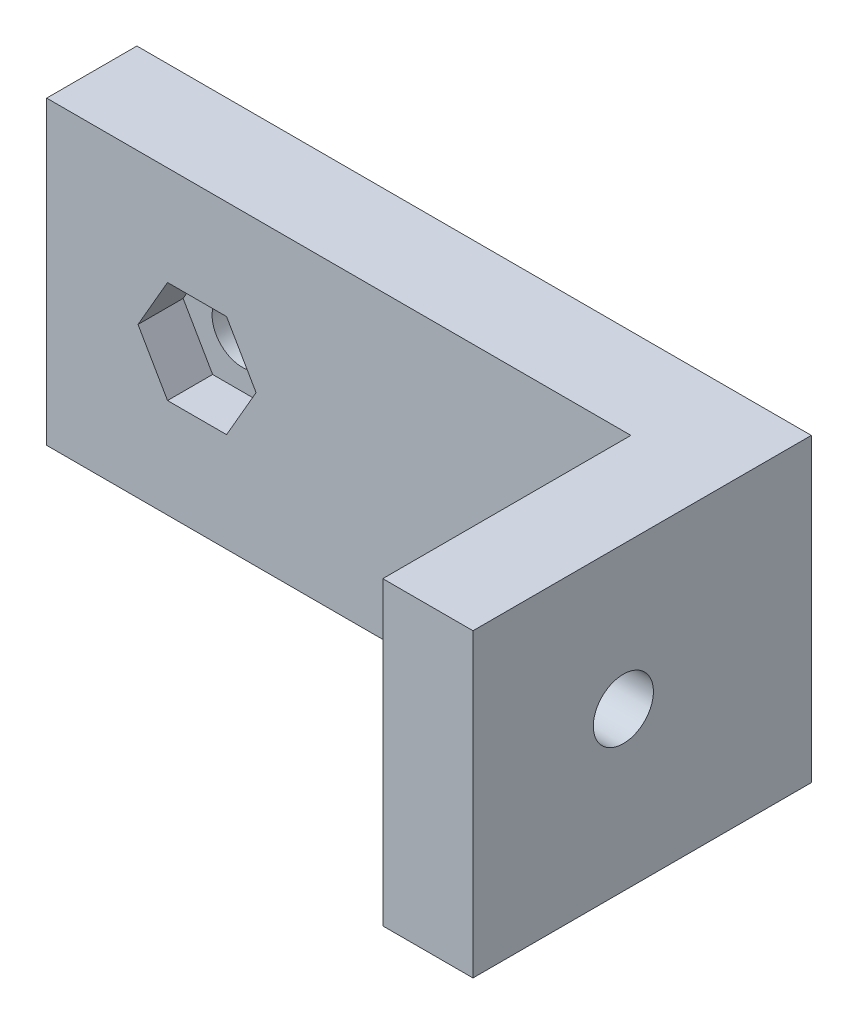
SolidWorks part; units mm, degrees
material "ABS"
ref_plane "Front Plane" through (0, 0, 0) normal (0, 0, 1) x (1, 0, 0)
ref_plane "Top Plane" through (0, 0, 0) normal (0, 1, 0) x (1, 0, 0)
ref_plane "Right Plane" through (0, 0, 0) normal (1, 0, 0) x (0, 0, -1)
sketch "Sketch1" plane through (0, 0, 0) normal (0, 0, 1) x (1, 0, 0)
  line L0 (169.7, 160.9919) -> (169.7, 86.2) construction
  line L1 (169.7, -7.5) -> (124.85, -7.5)
  line L2 (169.7, -7.5) -> (169.7, 12.5)
  line L3 (169.7, 12.5) -> (124.85, 12.5)
  line L4 (124.85, -7.5) -> (124.85, 12.5)
  line L5 (169.7, -7.5) -> (124.85, 12.5) construction
  line L6 (169.7, 12.5) -> (124.85, -7.5) construction
  line L8 (130.924, 2.5) -> (132.887, -0.9)
  line L9 (132.887, -0.9) -> (136.813, -0.9)
  line L10 (136.813, -0.9) -> (138.776, 2.5)
  line L11 (138.776, 2.5) -> (136.813, 5.9)
  line L12 (136.813, 5.9) -> (132.887, 5.9)
  line L13 (132.887, 5.9) -> (130.924, 2.5)
  circle A0 centre (134.85, 2.5) radius 2
  circle A1 centre (134.85, 2.5) radius 3.4 construction
  point P4 (147.275, 2.5)
  point P10 (134.85, 5.9)
  dimension "D2" = 10
  dimension "D3" = 10
  dimension "D4" = 10
  dimension "D1" = 6.8
extrude "Boss-Extrude1" add sketch "Sketch1" along normal blind 3 contours L4 L1 L2 L3 L13 L12 L11 L10 L9 L8 | L12 L13 L8 L9 L10 L11 A0 region at (147.8556, 2.5, 0) region at (131.9955, 4.1481, 0)
extrude "Boss-Extrude2" add sketch "Sketch1<4>" along normal blind 3 from surface contours L4 L1 L2 L3 L13 L12 L11 L10 L9 L8 region at (147.8556, 2.5, 0) starting at face at (147.275, 2.5, 3)
sketch "Sketch1<4>" plane through (0, 0, 0) normal (0, 0, 1) x (1, 0, 0) same geometry as "Sketch1"
sketch "Sketch5" plane through (169.7, 0, 0) normal (-1, 0, 0) x (0, 0, 1)
  line L0 (6, 12.5) -> (0, 12.5) construction
  line L1 (6, -7.5) -> (22.5, -7.5)
  line L2 (6, -7.5) -> (6, 12.5)
  line L3 (6, 12.5) -> (22.5, 12.5)
  line L4 (22.5, -7.5) -> (22.5, 12.5)
  line L5 (6, -7.5) -> (22.5, 12.5) construction
  line L6 (6, 12.5) -> (22.5, -7.5) construction
  line L8 (12.5, -0.926) -> (15.9, 1.037)
  line L9 (15.9, 1.037) -> (15.9, 4.963)
  line L10 (15.9, 4.963) -> (12.5, 6.926)
  line L11 (12.5, 6.926) -> (9.1, 4.963)
  line L12 (9.1, 4.963) -> (9.1, 1.037)
  line L13 (9.1, 1.037) -> (12.5, -0.926)
  circle A0 centre (12.5, 3) radius 2
  circle A1 centre (12.5, 3) radius 3.4 construction
  point P7 (14.25, 2.5)
  circle M18 centre (12.5, 3) radius 2
  dimension "D1" = 10
  dimension "D2" = 6.8
extrude "Boss-Extrude3" add sketch "Sketch5" along normal blind 3 contours L1 L4 L3 L2 L13 L12 L11 L10 L9 L8 | L12 L13 L8 L9 L10 L11 M18 region at (169.7, 2.5, 6.2593) region at (169.7, 0.1455, 10.8519)
extrude "Boss-Extrude4" add sketch "Sketch5<3>" along normal blind 3 from surface contours L1 L4 L3 L2 L13 L12 L11 L10 L9 L8 region at (169.7, 2.5, 6.2593) starting at face at (166.7, 2.5, 14.25)
sketch "Sketch5<3>" plane through (169.7, 0, 0) normal (-1, 0, 0) x (0, 0, 1) same geometry as "Sketch5"
